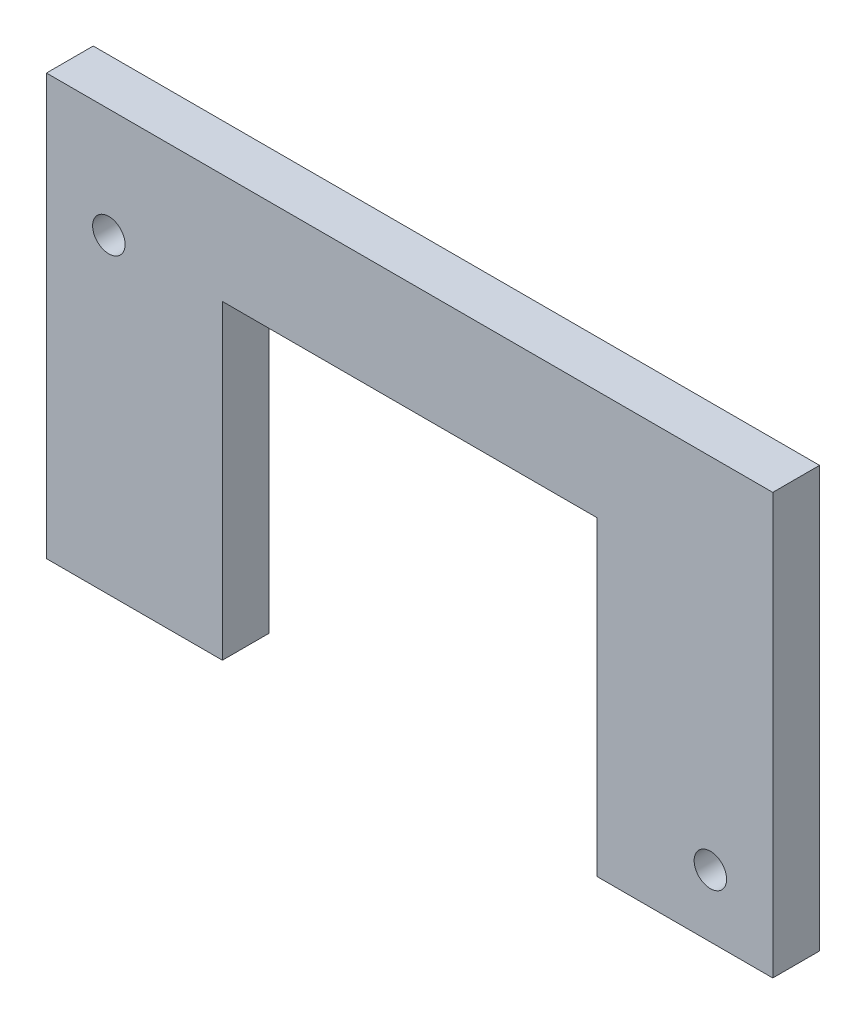
SolidWorks part; units mm, degrees
ref_plane "Front Plane" through (0, 0, 0) normal (0, 0, 1) x (1, 0, 0)
ref_plane "Top Plane" through (0, 0, 0) normal (0, 1, 0) x (1, 0, 0)
ref_plane "Right Plane" through (0, 0, 0) normal (1, 0, 0) x (0, 0, -1)
sketch "Sketch1" plane through (0, 0, 0) normal (0, 0, 1) x (1, 0, 0)
  line L1 (0, 0) -> (33.782, 0) construction
  line L2 (0, 0) -> (0, 19.812) construction
  line L3 (0, 19.812) -> (33.782, 19.812) construction
  line L4 (33.782, 0) -> (33.782, 19.812) construction
  line L5 (-1.5875, -1.5875) -> (35.3695, -1.5875)
  line L6 (-1.5875, -1.5875) -> (-1.5875, 19.812)
  line L7 (-1.5875, 19.812) -> (35.3695, 19.812)
  line L8 (35.3695, -1.5875) -> (35.3695, 19.812)
  circle A0 centre (1.5875, 14.2558) radius 0.8255
  circle A1 centre (32.1945, 1.5875) radius 0.8255
  dimension "D3" = 1.651
  dimension "0.065" = 1.651
  dimension "D5" = 1.5875
  dimension "D6" = 1.5875
  dimension "D7" = 1.5875
  dimension "D8" = 5.5562
  dimension "D9" = 3.175
  dimension "D11" = 3.175
  dimension "D12" = 5.5562
  dimension "D1" = 19.812
  dimension "D2" = 33.782
  dimension "D10" = 3.175
extrude "Boss-Extrude1" add sketch "Sketch1" along normal blind 2.3813
sketch "Sketch2" plane through (0, 0, 2.3813) normal (0, 0, 1) x (1, 0, 0)
  line L5 (-1.5875, -1.5875) -> (35.3695, -1.5875) construction
  line L6 (7.366, -1.5875) -> (26.416, -1.5875)
  line L7 (7.366, -1.5875) -> (7.366, 14.224)
  line L8 (7.366, 14.224) -> (26.416, 14.224)
  line L9 (26.416, -1.5875) -> (26.416, 14.224)
  line L10 (-1.5875, -1.5875) -> (7.366, -1.5875) construction
  line L11 (26.416, -1.5875) -> (35.3695, -1.5875) construction
  line L12 (35.3695, 19.812) -> (-1.5875, 19.812) construction
  dimension "D1" = 19.05
  dimension "D2" = 5.588
extrude "Cut-Extrude1" cut sketch "Sketch2" against normal up to next
